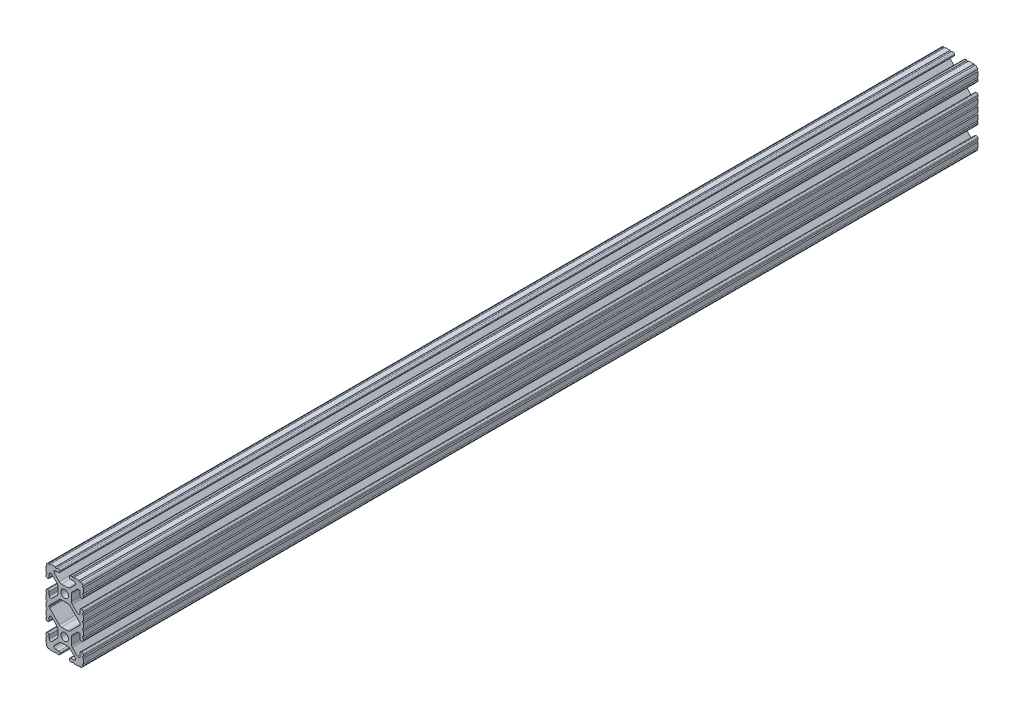
SolidWorks part; units mm, degrees
ref_plane "Front Plane" through (0, 0, 0) normal (0, 0, 1) x (1, 0, 0)
ref_plane "Top Plane" through (0, 0, 0) normal (0, 1, 0) x (1, 0, 0)
ref_plane "Right Plane" through (0, 0, 0) normal (1, 0, 0) x (0, 0, -1)
sketch "Sketch2" plane through (0, 0, 0) normal (0, 0, 1) x (1, 0, 0)
  line L0 (0, 25.4) -> (0, -25.4) construction
  line L1 (-12.7, 0) -> (12.7, 0) construction
  line L2 (3.2512, -25.4) -> (12.7, -25.4)
  line L3 (12.7, -25.4) -> (12.7, -15.9512)
  line L4 (3.2512, -25.4) -> (3.2512, -23.1902)
  line L5 (3.2512, -23.1902) -> (8.9276, -23.1902)
  line L6 (8.9276, -23.1902) -> (3.0856, -17.3482)
  line L7 (0, -12.7) -> (12.7, -25.4) construction
  line L8 (12.7, -15.9512) -> (10.4902, -15.9512)
  line L9 (10.4902, -15.9512) -> (10.4902, -21.6276)
  line L10 (10.4902, -21.6276) -> (4.6482, -15.7856)
  line L11 (3.2512, -25.4) -> (0, -25.4) construction
  line L12 (0, -25.4) -> (-3.2512, -25.4) construction
  line L13 (-3.2512, -25.4) -> (-12.7, -25.4) construction
  line L14 (12.7, 25.4) -> (-12.7, 25.4) construction
  line L15 (0, 12.7) -> (0, -12.7) construction
  circle A0 centre (0, -12.7) radius 2.6035
  arc A1 (6.3485, -23.1902) -> (7.1039, -21.3665) centre (6.3485, -22.1219) ccw construction
  point P8 (0, -17.3482)
  point P16 (-2.6035, -12.7)
  point P18 (2.6035, -12.7)
  point P19 (0, -10.0965)
  point P20 (0, -15.3035)
  point P27 (-12.7, -25.4)
  point P30 (0, 25.4)
  point P31 (12.7, 25.4)
  point P32 (-12.7, 25.4)
  point P33 (12.7, -25.4)
  point P34 (0, -12.7)
  point P35 (0, 12.7)
  point P37 (0, 0)
  point P38 (-3.2512, -25.4)
  point P39 (3.2512, -25.4)
  dimension "Center Hole Diameter" = 5.207
  dimension "Rail Height" = 50.8
  dimension "Rail Width" = 25.4
  dimension "T-Slot Width" = 6.5024
  dimension "Slot Inner Width" = 14.8336
  dimension "Thickness" = 2.2098
  dimension "Slot Depth" = 5.842
  dimension "D1" = 2.2098
  dimension "C to C" = 25.4
sketch "Sketch3" plane through (0, 0, 0) normal (1, 0, 0) x (0, 0, -1)
  line L0 (-304.8, -25.4) -> (304.8, -25.4) construction
  line L1 (-254, 0) -> (254, 0) construction
  point P6 (-304.8, -25.4)
  point P8 (-254, 0)
  point P9 (254, 0)
  point P10 (304.8, -25.4)
  dimension "Length" = 609.6
sketch "Sketch4" plane through (0, 0, 0) normal (0, 0, 1) x (1, 0, 0)
  line L0 (4.1904, -25.4) -> (10.1173, -25.4)
  line L1 (3.2512, -25.4) -> (12.7, -25.4) construction
  line L2 (3.2512, -25.4) -> (3.2512, -23.1902) construction
  line L3 (3.2512, -23.1902) -> (8.9276, -23.1902) construction
  line L4 (3.2512, -24.1294) -> (3.2512, -24.4608)
  line L5 (4.1904, -23.1902) -> (6.3485, -23.1902)
  line L6 (0, -17.3482) -> (2.164, -17.3482)
  line L7 (8.9276, -23.1902) -> (3.0856, -17.3482) construction
  line L8 (3.7373, -17.9999) -> (7.1039, -21.3665)
  line L9 (12.7, -25.4) -> (12.7, -15.9512) construction
  line L10 (10.4902, -21.6276) -> (4.6482, -15.7856) construction
  line L11 (10.4902, -15.9512) -> (10.4902, -21.6276) construction
  line L12 (10.4902, -19.0485) -> (10.4902, -16.8904)
  line L13 (12.7, -15.9512) -> (10.4902, -15.9512) construction
  line L14 (11.4294, -15.9512) -> (11.7608, -15.9512)
  line L15 (12.7, -16.8904) -> (12.7, -22.8173)
  line L16 (8.6665, -19.8039) -> (5.2999, -16.4373)
  line L17 (4.6482, -12.7) -> (4.6482, -14.864)
  line L19 (0, -17.3482) -> (0, -15.3035)
  line L20 (0, 25.4) -> (0, -25.4) construction
  line L21 (4.6482, -12.7) -> (2.6035, -12.7)
  arc A0 (3.2512, -24.4608) -> (4.1904, -25.4) centre (4.1904, -24.4608) ccw
  circle A1 centre (0, -12.7) radius 2.6035 construction
  arc A2 (3.2512, -24.1294) -> (4.1904, -23.1902) centre (4.1904, -24.1294) cw
  arc A3 (6.3485, -23.1902) -> (7.1039, -21.3665) centre (6.3485, -22.1219) ccw
  arc A4 (2.164, -17.3482) -> (3.7373, -17.9999) centre (2.164, -19.5732) cw
  arc A5 (10.1173, -25.4) -> (12.7, -22.8173) centre (10.1173, -22.8173) ccw
  arc A6 (8.6665, -19.8039) -> (10.4902, -19.0485) centre (9.4219, -19.0485) ccw
  arc A7 (10.4902, -16.8904) -> (11.4294, -15.9512) centre (11.4294, -16.8904) cw
  arc A8 (11.7608, -15.9512) -> (12.7, -16.8904) centre (11.7608, -16.8904) cw
  arc A9 (5.2999, -16.4373) -> (4.6482, -14.864) centre (6.8732, -14.864) cw
  arc A11 (0, -15.3035) -> (2.6035, -12.7) centre (0, -12.7) ccw
  dimension "D1" = 2.5827
  dimension "D2" = 2.225
  dimension "D3" = 0.9392
extrude "Boss-Extrude1" add sketch "Sketch4" along normal mid plane 609.6
sketch "Sketch5" plane through (0, 0, 0) normal (0, 0, 1) x (1, 0, 0)
  line L0 (3.2512, -25.4) -> (12.7, -25.4) construction
  line L1 (4.1904, -23.1902) -> (6.3485, -23.1902) construction
  line L3 (0, -12.7) -> (12.7, -25.4) construction
  line L4 (6.3485, -23.1902) -> (6.3485, -25.4) construction
  line L5 (8.9276, -23.1902) -> (3.0856, -17.3482) construction
  circle A0 centre (10.3562, -25.4) radius 0.5524
  circle A1 centre (5.796, -25.4) radius 0.5524
  circle A2 centre (12.7, -23.0562) radius 0.5524
  circle A3 centre (12.7, -18.496) radius 0.5524
  point P10 (5.2694, -23.1902)
  point P12 (9.4219, -19.0485)
  dimension "D1" = 1.1049
extrude "Cut-Extrude1" cut sketch "Sketch5" against normal through all both and the other way through all
mirror "Mirror1" about plane through (4.6482, -12.7, 304.8) normal (0, -1, 0) of bodies 137 134
sketch "Sketch6" plane through (0, 0, 0) normal (0, 0, 1) x (1, 0, 0)
  line L0 (12.7, -1.7914) -> (12.7, 0)
  line L1 (12.7, 0) -> (9.8037, 0)
  line L2 (-12.7, 0) -> (12.7, 0) construction
  line L3 (9.8037, 0) -> (9.8037, -2.3438)
  line L4 (9.8037, -2.3438) -> (12.1476, -2.3438)
  circle A0 centre (12.7, -2.3438) radius 0.5524 construction
  arc A1 (12.7, -1.7914) -> (12.1476, -2.3438) centre (12.7, -2.3438) ccw
  arc A4 (12.58, -1.8046) -> (12.7, -2.8963) centre (12.7, -2.3438) ccw construction
  arc A6 (9.8037, 0) -> (10.8954, -0.12) centre (10.3562, 0) ccw construction
extrude "Boss-Extrude2" add sketch "Sketch6" along normal mid plane 609.6
sketch "Sketch7" plane through (0, 0, 0) normal (0, 0, 1) x (1, 0, 0)
  line L0 (5.4206, -5.7168) -> (10.3284, -0.809)
  line L1 (3.7373, -7.4001) -> (7.1039, -4.0335) construction
  line L2 (10.4902, -0.4184) -> (10.4902, 0)
  line L3 (0, 0) -> (10.4902, 0)
  line L4 (-12.7, 0) -> (12.7, 0) construction
  line L5 (0, 0) -> (5.4206, -5.7168)
  arc A0 (10.3284, -0.809) -> (10.4902, -0.4184) centre (9.9377, -0.4184) ccw
  arc A3 (12.7, -1.7914) -> (12.7, -2.8963) centre (12.7, -2.3438) ccw construction
extrude "Cut-Extrude2" cut sketch "Sketch7" against normal through all both and the other way through all
mirror "Mirror2" about plane through (0, 0, 0) normal (0, 1, 0) of bodies 139 135
mirror "Mirror3" about plane through (0, 0, 0) normal (1, 0, 0) of bodies 136
equation "\"D1@Boss-Extrude1\"=\"Length@Sketch3\""
equation "\"D1@Sketch2\"=\"Thickness@Sketch2\""
equation "\"D2@Sketch4\"=\"Slot Inner Width@Sketch2\"*0.15"
equation "\"D1@Sketch4\"=\"D3@Sketch4\"*2.75"
equation "\"D3@Sketch4\"=\"Thickness@Sketch2\"*0.425"
equation "\"D1@Sketch5\"=\"Thickness@Sketch2\"*0.5"
equation "\"D1@Boss-Extrude2\"=\"Length@Sketch3\""
